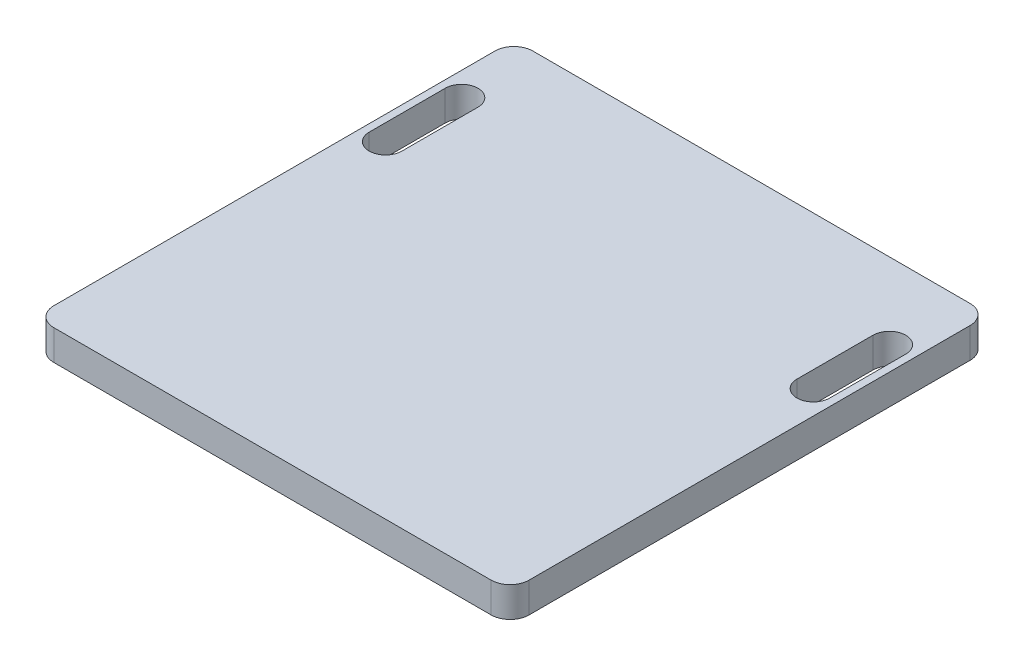
SolidWorks part; units mm, degrees
ref_plane "Front Plane" through (0, 0, 0) normal (0, 0, 1) x (1, 0, 0)
ref_plane "Top Plane" through (0, 0, 0) normal (0, 1, 0) x (1, 0, 0)
ref_plane "Right Plane" through (0, 0, 0) normal (1, 0, 0) x (0, 0, -1)
sketch "Sketch1" plane through (0, 0, 0) normal (0, 1, 0) x (1, 0, 0)
  line L0 (0, 0) -> (45, 0) construction
  line L1 (0, 0) -> (0, -8) construction
  line L2 (-2.5, 8) -> (47.5, 8)
  line L3 (-2.5, 8) -> (-2.5, -17.4)
  line L4 (-2.5, -17.4) -> (47.5, -17.4)
  line L5 (47.5, 8) -> (47.5, -17.4)
  line L6 (-2.5, -17.4) -> (47.5, -17.4)
  line L7 (-2.5, -17.4) -> (-2.5, -42.4)
  line L8 (-2.5, -42.4) -> (47.5, -42.4)
  line L9 (47.5, -17.4) -> (47.5, -42.4)
  line L10 (1.725, 0) -> (1.725, -8)
  line L11 (-1.725, 0) -> (-1.725, -8)
  line L12 (45, 0) -> (45, -8) construction
  line L13 (46.725, 0) -> (46.725, -8)
  line L14 (43.275, 0) -> (43.275, -8)
  circle A0 centre (0, 0) radius 1.725
  circle A1 centre (45, 0) radius 1.725
  arc A2 (1.725, 0) -> (-1.725, 0) centre (0, 0) ccw
  arc A3 (-1.725, -8) -> (1.725, -8) centre (0, -8) ccw
  arc A4 (46.725, 0) -> (43.275, 0) centre (45, 0) ccw
  arc A5 (43.275, -8) -> (46.725, -8) centre (45, -8) ccw
  point P9 (0, -4)
  point P17 (45, -4)
  point P23 (7.6248, 0)
  point P24 (0, 0)
  dimension "D2" = 3.45
  dimension "D1" = 45
  dimension "D3" = 50
  dimension "D5" = 25.4
  dimension "D6" = 25
  dimension "D7" = 2.5
  dimension "D8" = 8
  dimension "D4" = 8
extrude "Boss-Extrude1" add sketch "Sketch1" along normal blind 3.175 contours L5 L2 L3 L4 A0 A1 | L9 L4 L7 L8 region at (22.5, 0, 4.7432) region at (22.5, 0, 29.9)
fillet "Fillet1" radius 2 4 edges at (47.5, 1.5875, -8) (-2.5, 1.5875, -8) (47.5, 1.5875, 42.4) (-2.5, 1.5875, 42.4)
equation "\"D7@Sketch1\"=(\"D3@Sketch1\"-\"D1@Sketch1\")/2"
